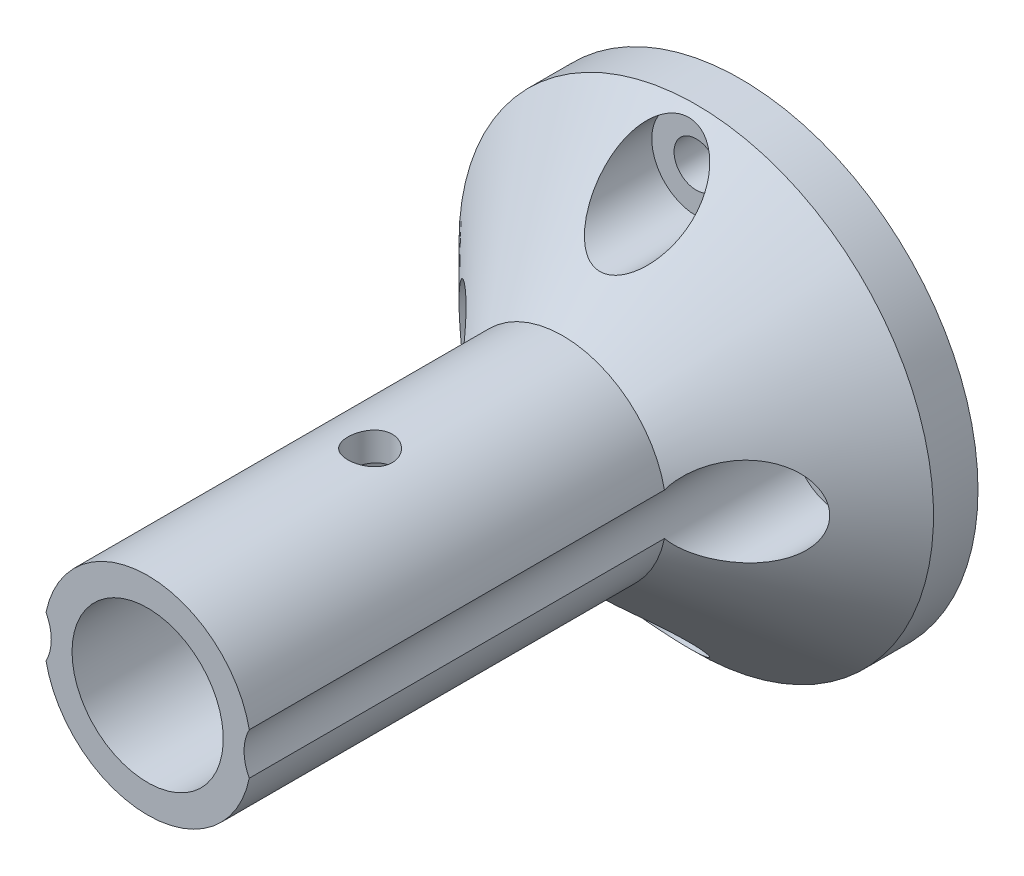
SolidWorks part; units mm, degrees
ref_plane "前视基准面" through (0, 0, 0) normal (0, 0, 1) x (1, 0, 0)
ref_plane "上视基准面" through (0, 0, 0) normal (0, 1, 0) x (1, 0, 0)
ref_plane "右视基准面" through (0, 0, 0) normal (1, 0, 0) x (0, 0, -1)
other "Configuration Table"
sketch "草图1" plane through (0, 0, 0) normal (0, 0, 1) x (1, 0, 0)
  circle A0 centre (0, 0) radius 16
  dimension "D1" = 32
extrude "凸台-拉伸1" add sketch "草图1" along normal blind 40
sketch "草图2" plane through (0, 0, 0) normal (0, 1, 0) x (1, 0, 0)
  line L0 (0, 0) -> (0, -20) construction
  line L1 (-16, -40) -> (-16, -3)
  line L2 (-16, 0) -> (-16, -40) construction
  line L3 (-16, -3) -> (-7, -12)
  line L4 (-7, -12) -> (-7, -40)
  line L5 (-16, -40) -> (16, -40) construction
  line L6 (-7, -40) -> (-16, -40)
  line L7 (16, 0) -> (-16, 0) construction
  line L8 (0, 0) -> (-5.1, 0)
  line L9 (0, 0) -> (0, -40)
  line L10 (0, -40) -> (-5.1, -40)
  line L11 (-5.1, 0) -> (-5.1, -40)
  point P16 (0, 0)
  point P17 (-5, 0)
  dimension "D1" = 20
  dimension "D2" = 45
  dimension "D3" = 7
  dimension "D4" = 3
  dimension "D5" = 5.1
revolve "切除-旋转1" cut sketch "草图2" angle 360 about L0
sketch "草图3" plane through (0, 0, 0) normal (0, 0, 1) x (1, 0, 0)
  circle A0 centre (0, -12.5) radius 1.5 construction
  circle A1 centre (-9.5, 0) radius 1.5 construction
  circle A2 centre (9.5, 0) radius 1.5 construction
  circle A3 centre (0, 12.5) radius 1.5 construction
  circle A4 centre (0, -12.5) radius 1.5
  circle A5 centre (-9.5, 0) radius 1.5
  circle A6 centre (9.5, 0) radius 1.5
  circle A7 centre (0, 12.5) radius 1.5
extrude "切除-拉伸2" cut sketch "草图3" along normal through all
ref_plane "基准面1" through (0, 0, 3) normal (0, 0, 1) x (1, 0, 0)
sketch "草图4" plane through (0, 0, 3) normal (0, 0, 1) x (1, 0, 0)
  circle A0 centre (0, -12.5) radius 1.5 construction
  circle A1 centre (9.5, 0) radius 1.5 construction
  circle A2 centre (-9.5, 0) radius 1.5 construction
  circle A3 centre (0, 12.5) radius 1.5 construction
  circle A4 centre (0, -12.5) radius 1.5
  circle A5 centre (9.5, 0) radius 1.5
  circle A6 centre (-9.5, 0) radius 1.5
  circle A7 centre (0, 12.5) radius 1.5
  circle A8 centre (0, 12.5) radius 3
  circle A9 centre (-9.5, 0) radius 3
  circle A10 centre (9.5, 0) radius 3
  circle A11 centre (0, -12.5) radius 3
  dimension "D1" = 1.5
extrude "切除-拉伸3" cut sketch "草图4" along normal through all contours A5 | A6 | A7 | A4 | A9 | A10 | A8 | A11
sketch "草图5" plane through (0, 0, 0) normal (0, 1, 0) x (1, 0, 0)
  line L1 (-6.8553, -40) -> (6.8553, -40) construction
  circle A0 centre (0, -25) radius 1.5
  point P4 (0, -40)
  dimension "D2" = 3
  dimension "D1" = 15
extrude "切除-拉伸4" cut sketch "草图5" against normal through all and the other way through all
